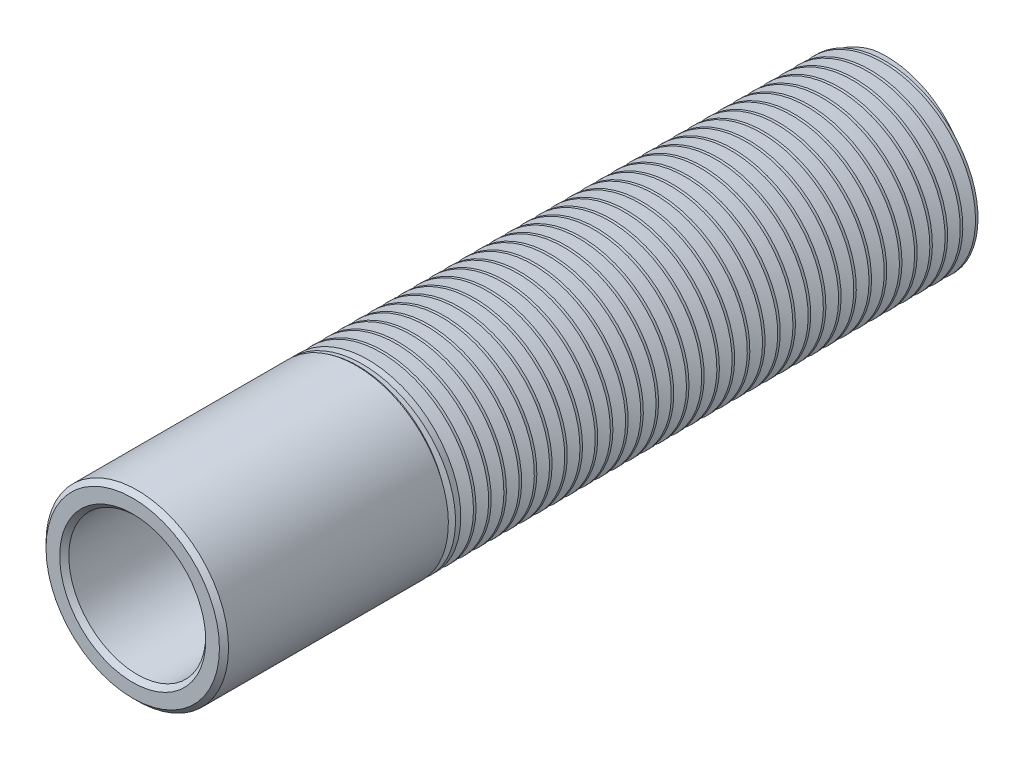
SolidWorks part; units mm, degrees
ref_plane "Front Plane" through (0, 0, 0) normal (0, 0, 1) x (1, 0, 0)
ref_plane "Top Plane" through (0, 0, 0) normal (0, 1, 0) x (1, 0, 0)
ref_plane "Right Plane" through (0, 0, 0) normal (1, 0, 0) x (0, 0, -1)
sketch "Sketch1" plane through (0, 0, 0) normal (0, 0, 1) x (1, 0, 0)
  circle A0 centre (0, 0) radius 6
  circle A1 centre (0, 0) radius 4.5
  dimension "D1" = 12
  dimension "D2" = 9
extrude "Boss-Extrude1" add sketch "Sketch1" along normal blind 50
chamfer "Chamfer1" distance 0.3 angle 45 4 edges at (6, 0, 0) (4.5, 0, 0) (6, 0, 50) (4.5, 0, 50)
ref_plane "Plane1" through (0, 0, -1) normal (0, 0, -1) x (-1, 0, 0)
sketch "Sketch2" plane through (0, 0, -1) normal (0, 0, -1) x (-1, 0, 0)
  circle A0 centre (0, 0) radius 6
  dimension "D1" = 12
curve "Helix/Spiral1" pitch 1 height 36 turns 36
sketch "Sketch3" plane through (0, 0, 0) normal (0, 1, 0) x (1, 0, 0)
  line L0 (6.27, 1) -> (-6.27, 1) construction
  line L1 (-6, 1) -> (-5.04, 1) construction
  line L2 (-6, 1) -> (-6, 1.96) construction
  line L3 (-6, 1.96) -> (-5.04, 1.96) construction
  line L4 (-5.04, 1) -> (-5.04, 1.96) construction
  line L5 (-6, 1.48) -> (-5.04, 1.48) construction
  line L6 (-5.0751, 1.5561) -> (-6, 1.8968)
  line L8 (-6, 1.8968) -> (-6, 1.0632)
  line L9 (-5.0751, 1.4039) -> (-6, 1.0632)
  arc A0 (-5.0751, 1.4039) -> (-5.0751, 1.5561) centre (-5.14, 1.48) ccw
  spline S0 degree 3 poles (-6, 1) (-6, 0.9793) (-5.6876, 0.9374) (-4.3531, 0.875) (-2.3559, 0.8125) (0, 0.75) (2.3559, 0.6875) (4.3531, 0.625) (5.6876, 0.5625) (6.1562, 0.5) (5.6876, 0.4375) (4.3531, 0.375) (2.3559, 0.3125) (0, 0.25) (-2.3559, 0.1875) (-4.3531, 0.125) (-5.6876, 0.0625) (-6.1562, 0) (-5.6876, -0.0625) (-4.3531, -0.125) (-2.3559, -0.1875) (0, -0.25) (2.3559, -0.3125) (4.3531, -0.375) (5.6876, -0.4375) (6.1562, -0.5) (5.6876, -0.5625) (4.3531, -0.625) (2.3559, -0.6875) (0, -0.75) (-2.3559, -0.8125) (-4.3531, -0.875) (-5.6876, -0.9375) (-6.1562, -1) (-5.6876, -1.0625) (-4.3531, -1.125) (-2.3559, -1.1875) (0, -1.25) (2.3559, -1.3125) (4.3531, -1.375) (5.6876, -1.4375) (6.1562, -1.5) (5.6876, -1.5625) (4.3531, -1.625) (2.3559, -1.6875) (0, -1.75) (-2.3559, -1.8125) (-4.3531, -1.875) (-5.6876, -1.9375) (-6.1562, -2) (-5.6876, -2.0625) (-4.3531, -2.125) (-2.3559, -2.1875) (0, -2.25) (2.3559, -2.3125) (4.3531, -2.375) (5.6876, -2.4375) (6.1562, -2.5) (5.6876, -2.5625) (4.3531, -2.625) (2.3559, -2.6875) (0, -2.75) (-2.3559, -2.8125) (-4.3531, -2.875) (-5.6876, -2.9375) (-6.1562, -3) (-5.6876, -3.0625) (-4.3531, -3.125) (-2.3559, -3.1875) (0, -3.25) (2.3559, -3.3125) (4.3531, -3.375) (5.6876, -3.4375) (6.1562, -3.5) (5.6876, -3.5625) (4.3531, -3.625) (2.3559, -3.6875) (0, -3.75) (-2.3559, -3.8125) (-4.3531, -3.875) (-5.6876, -3.9375) (-6.1562, -4) (-5.6876, -4.0625) (-4.3531, -4.125) (-2.3559, -4.1875) (0, -4.25) (2.3559, -4.3125) (4.3531, -4.375) (5.6876, -4.4375) (6.1562, -4.5) (5.6876, -4.5625) (4.3531, -4.625) (2.3559, -4.6875) (0, -4.75) (-2.3559, -4.8125) (-4.3531, -4.875) (-5.6876, -4.9375) (-6.1562, -5) (-5.6876, -5.0625) (-4.3531, -5.125) (-2.3559, -5.1875) (0, -5.25) (2.3559, -5.3125) (4.3531, -5.375) (5.6876, -5.4375) (6.1562, -5.5) (5.6876, -5.5625) (4.3531, -5.625) (2.3559, -5.6875) (0, -5.75) (-2.3559, -5.8125) (-4.3531, -5.875) (-5.6876, -5.9375) (-6.1562, -6) (-5.6876, -6.0625) (-4.3531, -6.125) (-2.3559, -6.1875) (0, -6.25) (2.3559, -6.3125) (4.3531, -6.375) (5.6876, -6.4375) (6.1562, -6.5) (5.6876, -6.5625) (4.3531, -6.625) (2.3559, -6.6875) (0, -6.75) (-2.3559, -6.8125) (-4.3531, -6.875) (-5.6876, -6.9375) (-6.1562, -7) (-5.6876, -7.0625) (-4.3531, -7.125) (-2.3559, -7.1875) (0, -7.25) (2.3559, -7.3125) (4.3531, -7.375) (5.6876, -7.4375) (6.1562, -7.5) (5.6876, -7.5625) (4.3531, -7.625) (2.3559, -7.6875) (0, -7.75) (-2.3559, -7.8125) (-4.3531, -7.875) (-5.6876, -7.9375) (-6.1562, -8) (-5.6876, -8.0625) (-4.3531, -8.125) (-2.3559, -8.1875) (0, -8.25) (2.3559, -8.3125) (4.3531, -8.375) (5.6876, -8.4375) (6.1562, -8.5) (5.6876, -8.5625) (4.3531, -8.625) (2.3559, -8.6875) (0, -8.75) (-2.3559, -8.8125) (-4.3531, -8.875) (-5.6876, -8.9375) (-6.1562, -9) (-5.6876, -9.0625) (-4.3531, -9.125) (-2.3559, -9.1875) (0, -9.25) (2.3559, -9.3125) (4.3531, -9.375) (5.6876, -9.4375) (6.1562, -9.5) (5.6876, -9.5625) (4.3531, -9.625) (2.3559, -9.6875) (0, -9.75) (-2.3559, -9.8125) (-4.3531, -9.875) (-5.6876, -9.9375) (-6.1562, -10) (-5.6876, -10.0625) (-4.3531, -10.125) (-2.3559, -10.1875) (0, -10.25) (2.3559, -10.3125) (4.3531, -10.375) (5.6876, -10.4375) (6.1562, -10.5) (5.6876, -10.5625) (4.3531, -10.625) (2.3559, -10.6875) (0, -10.75) (-2.3559, -10.8125) (-4.3531, -10.875) (-5.6876, -10.9375) (-6.1562, -11) (-5.6876, -11.0625) (-4.3531, -11.125) (-2.3559, -11.1875) (0, -11.25) (2.3559, -11.3125) (4.3531, -11.375) (5.6876, -11.4375) (6.1562, -11.5) (5.6876, -11.5625) (4.3531, -11.625) (2.3559, -11.6875) (0, -11.75) (-2.3559, -11.8125) (-4.3531, -11.875) (-5.6876, -11.9375) (-6.1562, -12) (-5.6876, -12.0625) (-4.3531, -12.125) (-2.3559, -12.1875) (0, -12.25) (2.3559, -12.3125) (4.3531, -12.375) (5.6876, -12.4375) (6.1562, -12.5) (5.6876, -12.5625) (4.3531, -12.625) (2.3559, -12.6875) (0, -12.75) (-2.3559, -12.8125) (-4.3531, -12.875) (-5.6876, -12.9375) (-6.1562, -13) (-5.6876, -13.0625) (-4.3531, -13.125) (-2.3559, -13.1875) (0, -13.25) (2.3559, -13.3125) (4.3531, -13.375) (5.6876, -13.4375) (6.1562, -13.5) (5.6876, -13.5625) (4.3531, -13.625) (2.3559, -13.6875) (0, -13.75) (-2.3559, -13.8125) (-4.3531, -13.875) (-5.6876, -13.9375) (-6.1562, -14) (-5.6876, -14.0625) (-4.3531, -14.125) (-2.3559, -14.1875) (0, -14.25) (2.3559, -14.3125) (4.3531, -14.375) (5.6876, -14.4375) (6.1562, -14.5) (5.6876, -14.5625) (4.3531, -14.625) (2.3559, -14.6875) (0, -14.75) (-2.3559, -14.8125) (-4.3531, -14.875) (-5.6876, -14.9375) (-6.1562, -15) (-5.6876, -15.0625) (-4.3531, -15.125) (-2.3559, -15.1875) (0, -15.25) (2.3559, -15.3125) (4.3531, -15.375) (5.6876, -15.4375) (6.1562, -15.5) (5.6876, -15.5625) (4.3531, -15.625) (2.3559, -15.6875) (0, -15.75) (-2.3559, -15.8125) (-4.3531, -15.875) (-5.6876, -15.9375) (-6.1562, -16) (-5.6876, -16.0625) (-4.3531, -16.125) (-2.3559, -16.1875) (0, -16.25) (2.3559, -16.3125) (4.3531, -16.375) (5.6876, -16.4375) (6.1562, -16.5) (5.6876, -16.5625) (4.3531, -16.625) (2.3559, -16.6875) (0, -16.75) (-2.3559, -16.8125) (-4.3531, -16.875) (-5.6876, -16.9375) (-6.1562, -17) (-5.6876, -17.0625) (-4.3531, -17.125) (-2.3559, -17.1875) (0, -17.25) (2.3559, -17.3125) (4.3531, -17.375) (5.6876, -17.4375) (6.1562, -17.5) (5.6876, -17.5625) (4.3531, -17.625) (2.3559, -17.6875) (0, -17.75) (-2.3559, -17.8125) (-4.3531, -17.875) (-5.6876, -17.9375) (-6.1562, -18) (-5.6876, -18.0625) (-4.3531, -18.125) (-2.3559, -18.1875) (0, -18.25) (2.3559, -18.3125) (4.3531, -18.375) (5.6876, -18.4375) (6.1562, -18.5) (5.6876, -18.5625) (4.3531, -18.625) (2.3559, -18.6875) (0, -18.75) (-2.3559, -18.8125) (-4.3531, -18.875) (-5.6876, -18.9375) (-6.1562, -19) (-5.6876, -19.0625) (-4.3531, -19.125) (-2.3559, -19.1875) (0, -19.25) (2.3559, -19.3125) (4.3531, -19.375) (5.6876, -19.4375) (6.1562, -19.5) (5.6876, -19.5625) (4.3531, -19.625) (2.3559, -19.6875) (0, -19.75) (-2.3559, -19.8125) (-4.3531, -19.875) (-5.6876, -19.9375) (-6.1562, -20) (-5.6876, -20.0625) (-4.3531, -20.125) (-2.3559, -20.1875) (0, -20.25) (2.3559, -20.3125) (4.3531, -20.375) (5.6876, -20.4375) (6.1562, -20.5) (5.6876, -20.5625) (4.3531, -20.625) (2.3559, -20.6875) (0, -20.75) (-2.3559, -20.8125) (-4.3531, -20.875) (-5.6876, -20.9375) (-6.1562, -21) (-5.6876, -21.0625) (-4.3531, -21.125) (-2.3559, -21.1875) (0, -21.25) (2.3559, -21.3125) (4.3531, -21.375) (5.6876, -21.4375) (6.1562, -21.5) (5.6876, -21.5625) (4.3531, -21.625) (2.3559, -21.6875) (0, -21.75) (-2.3559, -21.8125) (-4.3531, -21.875) (-5.6876, -21.9375) (-6.1562, -22) (-5.6876, -22.0625) (-4.3531, -22.125) (-2.3559, -22.1875) (0, -22.25) (2.3559, -22.3125) (4.3531, -22.375) (5.6876, -22.4375) (6.1562, -22.5) (5.6876, -22.5625) (4.3531, -22.625) (2.3559, -22.6875) (0, -22.75) (-2.3559, -22.8125) (-4.3531, -22.875) (-5.6876, -22.9375) (-6.1562, -23) (-5.6876, -23.0625) (-4.3531, -23.125) (-2.3559, -23.1875) (0, -23.25) (2.3559, -23.3125) (4.3531, -23.375) (5.6876, -23.4375) (6.1562, -23.5) (5.6876, -23.5625) (4.3531, -23.625) (2.3559, -23.6875) (0, -23.75) (-2.3559, -23.8125) (-4.3531, -23.875) (-5.6876, -23.9375) (-6.1562, -24) (-5.6876, -24.0625) (-4.3531, -24.125) (-2.3559, -24.1875) (0, -24.25) (2.3559, -24.3125) (4.3531, -24.375) (5.6876, -24.4375) (6.1562, -24.5) (5.6876, -24.5625) (4.3531, -24.625) (2.3559, -24.6875) (0, -24.75) (-2.3559, -24.8125) (-4.3531, -24.875) (-5.6876, -24.9375) (-6.1562, -25) (-5.6876, -25.0625) (-4.3531, -25.125) (-2.3559, -25.1875) (0, -25.25) (2.3559, -25.3125) (4.3531, -25.375) (5.6876, -25.4375) (6.1562, -25.5) (5.6876, -25.5625) (4.3531, -25.625) (2.3559, -25.6875) (0, -25.75) (-2.3559, -25.8125) (-4.3531, -25.875) (-5.6876, -25.9375) (-6.1562, -26) (-5.6876, -26.0625) (-4.3531, -26.125) (-2.3559, -26.1875) (0, -26.25) (2.3559, -26.3125) (4.3531, -26.375) (5.6876, -26.4375) (6.1562, -26.5) (5.6876, -26.5625) (4.3531, -26.625) (2.3559, -26.6875) (0, -26.75) (-2.3559, -26.8125) (-4.3531, -26.875) (-5.6876, -26.9375) (-6.1562, -27) (-5.6876, -27.0625) (-4.3531, -27.125) (-2.3559, -27.1875) (0, -27.25) (2.3559, -27.3125) (4.3531, -27.375) (5.6876, -27.4375) (6.1562, -27.5) (5.6876, -27.5625) (4.3531, -27.625) (2.3559, -27.6875) (0, -27.75) (-2.3559, -27.8125) (-4.3531, -27.875) (-5.6876, -27.9375) (-6.1562, -28) (-5.6876, -28.0625) (-4.3531, -28.125) (-2.3559, -28.1875) (0, -28.25) (2.3559, -28.3125) (4.3531, -28.375) (5.6876, -28.4375) (6.1562, -28.5) (5.6876, -28.5625) (4.3531, -28.625) (2.3559, -28.6875) (0, -28.75) (-2.3559, -28.8125) (-4.3531, -28.875) (-5.6876, -28.9375) (-6.1562, -29) (-5.6876, -29.0625) (-4.3531, -29.125) (-2.3559, -29.1875) (0, -29.25) (2.3559, -29.3125) (4.3531, -29.375) (5.6876, -29.4375) (6.1562, -29.5) (5.6876, -29.5625) (4.3531, -29.625) (2.3559, -29.6875) (0, -29.75) (-2.3559, -29.8125) (-4.3531, -29.875) (-5.6876, -29.9375) (-6.1562, -30) (-5.6876, -30.0625) (-4.3531, -30.125) (-2.3559, -30.1875) (0, -30.25) (2.3559, -30.3125) (4.3531, -30.375) (5.6876, -30.4375) (6.1562, -30.5) (5.6876, -30.5625) (4.3531, -30.625) (2.3559, -30.6875) (0, -30.75) (-2.3559, -30.8125) (-4.3531, -30.875) (-5.6876, -30.9375) (-6.1562, -31) (-5.6876, -31.0625) (-4.3531, -31.125) (-2.3559, -31.1875) (0, -31.25) (2.3559, -31.3125) (4.3531, -31.375) (5.6876, -31.4375) (6.1562, -31.5) (5.6876, -31.5625) (4.3531, -31.625) (2.3559, -31.6875) (0, -31.75) (-2.3559, -31.8125) (-4.3531, -31.875) (-5.6876, -31.9375) (-6.1562, -32) (-5.6876, -32.0625) (-4.3531, -32.125) (-2.3559, -32.1875) (0, -32.25) (2.3559, -32.3125) (4.3531, -32.375) (5.6876, -32.4375) (6.1562, -32.5) (5.6876, -32.5625) (4.3531, -32.625) (2.3559, -32.6875) (0, -32.75) (-2.3559, -32.8125) (-4.3531, -32.875) (-5.6876, -32.9375) (-6.1562, -33) (-5.6876, -33.0625) (-4.3531, -33.125) (-2.3559, -33.1875) (0, -33.25) (2.3559, -33.3125) (4.3531, -33.375) (5.6876, -33.4375) (6.1562, -33.5) (5.6876, -33.5625) (4.3531, -33.625) (2.3559, -33.6875) (0, -33.75) (-2.3559, -33.8125) (-4.3531, -33.875) (-5.6876, -33.9375) (-6.1562, -34) (-5.6876, -34.0625) (-4.3531, -34.125) (-2.3559, -34.1875) (0, -34.25) (2.3559, -34.3125) (4.3531, -34.375) (5.6876, -34.4375) (6.1562, -34.5) (5.6876, -34.5625) (4.3531, -34.625) (2.3559, -34.6875) (0, -34.75) (-2.3559, -34.8125) (-4.3531, -34.875) (-5.6876, -34.9374) (-6, -34.9793) (-6, -35) knots 0 0 0 0 0.001736 0.003472 0.005208 0.006944 0.008681 0.010417 0.012153 0.013889 0.015625 0.017361 0.019097 0.020833 0.022569 0.024306 0.026042 0.027778 0.029514 0.03125 0.032986 0.034722 0.036458 0.038194 0.039931 0.041667 0.043403 0.045139 0.046875 0.048611 0.050347 0.052083 0.053819 0.055556 0.057292 0.059028 0.060764 0.0625 0.064236 0.065972 0.067708 0.069444 0.071181 0.072917 0.074653 0.076389 0.078125 0.079861 0.081597 0.083333 0.085069 0.086806 0.088542 0.090278 0.092014 0.09375 0.095486 0.097222 0.098958 0.100694 0.102431 0.104167 0.105903 0.107639 0.109375 0.111111 0.112847 0.114583 0.116319 0.118056 0.119792 0.121528 0.123264 0.125 0.126736 0.128472 0.130208 0.131944 0.133681 0.135417 0.137153 0.138889 0.140625 0.142361 0.144097 0.145833 0.147569 0.149306 0.151042 0.152778 0.154514 0.15625 0.157986 0.159722 0.161458 0.163194 0.164931 0.166667 0.168403 0.170139 0.171875 0.173611 0.175347 0.177083 0.178819 0.180556 0.182292 0.184028 0.185764 0.1875 0.189236 0.190972 0.192708 0.194444 0.196181 0.197917 0.199653 0.201389 0.203125 0.204861 0.206597 0.208333 0.210069 0.211806 0.213542 0.215278 0.217014 0.21875 0.220486 0.222222 0.223958 0.225694 0.227431 0.229167 0.230903 0.232639 0.234375 0.236111 0.237847 0.239583 0.241319 0.243056 0.244792 0.246528 0.248264 0.25 0.251736 0.253472 0.255208 0.256944 0.258681 0.260417 0.262153 0.263889 0.265625 0.267361 0.269097 0.270833 0.272569 0.274306 0.276042 0.277778 0.279514 0.28125 0.282986 0.284722 0.286458 0.288194 0.289931 0.291667 0.293403 0.295139 0.296875 0.298611 0.300347 0.302083 0.303819 0.305556 0.307292 0.309028 0.310764 0.3125 0.314236 0.315972 0.317708 0.319444 0.321181 0.322917 0.324653 0.326389 0.328125 0.329861 0.331597 0.333333 0.335069 0.336806 0.338542 0.340278 0.342014 0.34375 0.345486 0.347222 0.348958 0.350694 0.352431 0.354167 0.355903 0.357639 0.359375 0.361111 0.362847 0.364583 0.366319 0.368056 0.369792 0.371528 0.373264 0.375 0.376736 0.378472 0.380208 0.381944 0.383681 0.385417 0.387153 0.388889 0.390625 0.392361 0.394097 0.395833 0.397569 0.399306 0.401042 0.402778 0.404514 0.40625 0.407986 0.409722 0.411458 0.413194 0.414931 0.416667 0.418403 0.420139 0.421875 0.423611 0.425347 0.427083 0.428819 0.430556 0.432292 0.434028 0.435764 0.4375 0.439236 0.440972 0.442708 0.444444 0.446181 0.447917 0.449653 0.451389 0.453125 0.454861 0.456597 0.458333 0.460069 0.461806 0.463542 0.465278 0.467014 0.46875 0.470486 0.472222 0.473958 0.475694 0.477431 0.479167 0.480903 0.482639 0.484375 0.486111 0.487847 0.489583 0.491319 0.493056 0.494792 0.496528 0.498264 0.5 0.501736 0.503472 0.505208 0.506944 0.508681 0.510417 0.512153 0.513889 0.515625 0.517361 0.519097 0.520833 0.522569 0.524306 0.526042 0.527778 0.529514 0.53125 0.532986 0.534722 0.536458 0.538194 0.539931 0.541667 0.543403 0.545139 0.546875 0.548611 0.550347 0.552083 0.553819 0.555556 0.557292 0.559028 0.560764 0.5625 0.564236 0.565972 0.567708 0.569444 0.571181 0.572917 0.574653 0.576389 0.578125 0.579861 0.581597 0.583333 0.585069 0.586806 0.588542 0.590278 0.592014 0.59375 0.595486 0.597222 0.598958 0.600694 0.602431 0.604167 0.605903 0.607639 0.609375 0.611111 0.612847 0.614583 0.616319 0.618056 0.619792 0.621528 0.623264 0.625 0.626736 0.628472 0.630208 0.631944 0.633681 0.635417 0.637153 0.638889 0.640625 0.642361 0.644097 0.645833 0.647569 0.649306 0.651042 0.652778 0.654514 0.65625 0.657986 0.659722 0.661458 0.663194 0.664931 0.666667 0.668403 0.670139 0.671875 0.673611 0.675347 0.677083 0.678819 0.680556 0.682292 0.684028 0.685764 0.6875 0.689236 0.690972 0.692708 0.694444 0.696181 0.697917 0.699653 0.701389 0.703125 0.704861 0.706597 0.708333 0.710069 0.711806 0.713542 0.715278 0.717014 0.71875 0.720486 0.722222 0.723958 0.725694 0.727431 0.729167 0.730903 0.732639 0.734375 0.736111 0.737847 0.739583 0.741319 0.743056 0.744792 0.746528 0.748264 0.75 0.751736 0.753472 0.755208 0.756944 0.758681 0.760417 0.762153 0.763889 0.765625 0.767361 0.769097 0.770833 0.772569 0.774306 0.776042 0.777778 0.779514 0.78125 0.782986 0.784722 0.786458 0.788194 0.789931 0.791667 0.793403 0.795139 0.796875 0.798611 0.800347 0.802083 0.803819 0.805556 0.807292 0.809028 0.810764 0.8125 0.814236 0.815972 0.817708 0.819444 0.821181 0.822917 0.824653 0.826389 0.828125 0.829861 0.831597 0.833333 0.835069 0.836806 0.838542 0.840278 0.842014 0.84375 0.845486 0.847222 0.848958 0.850694 0.852431 0.854167 0.855903 0.857639 0.859375 0.861111 0.862847 0.864583 0.866319 0.868056 0.869792 0.871528 0.873264 0.875 0.876736 0.878472 0.880208 0.881944 0.883681 0.885417 0.887153 0.888889 0.890625 0.892361 0.894097 0.895833 0.897569 0.899306 0.901042 0.902778 0.904514 0.90625 0.907986 0.909722 0.911458 0.913194 0.914931 0.916667 0.918403 0.920139 0.921875 0.923611 0.925347 0.927083 0.928819 0.930556 0.932292 0.934028 0.935764 0.9375 0.939236 0.940972 0.942708 0.944444 0.946181 0.947917 0.949653 0.951389 0.953125 0.954861 0.956597 0.958333 0.960069 0.961806 0.963542 0.965278 0.967014 0.96875 0.970486 0.972222 0.973958 0.975694 0.977431 0.979167 0.980903 0.982639 0.984375 0.986111 0.987847 0.989583 0.991319 0.993056 0.994792 0.996528 0.998264 1 1 1 1 construction
  dimension "D3" = 0.2
  dimension "D1" = 0.96
  dimension "D2" = 0.96
sweep "Cut-Sweep2" cut profiles "Sketch3" path "Helix/Spiral1"
ref_plane "Plane2" through (0, 0, 35) normal (0, 0, -1) x (-1, 0, 0)
sketch "Sketch4" plane through (0, 0, 35) normal (0, 0, -1) x (-1, 0, 0)
  circle A0 centre (0, 0) radius 6
  dimension "D1" = 12
curve "Helix/Spiral2"
sketch "Sketch5" plane through (0, 0, 0) normal (0, 1, 0) x (1, 0, 0)
  line L3 (-6, -34.1032) -> (-6, -34.9368)
  line L4 (-6, -34.9368) -> (-5.0751, -34.5961)
  line L5 (-5.0751, -34.4439) -> (-6, -34.1032)
  line L6 (-6, -34.1032) -> (-6, -34.9368)
  line L7 (-6, -34.9368) -> (-5.0751, -34.5961)
  line L8 (-5.0751, -34.4439) -> (-6, -34.1032)
  arc A1 (-5.0751, -34.5961) -> (-5.0751, -34.4439) centre (-5.14, -34.52) ccw
  arc A2 (-5.0751, -34.5961) -> (-5.0751, -34.4439) centre (-5.14, -34.52) ccw
  dimension "D1" = 0
sweep "Cut-Sweep3" cut profiles "Sketch5" path "Helix/Spiral2"
